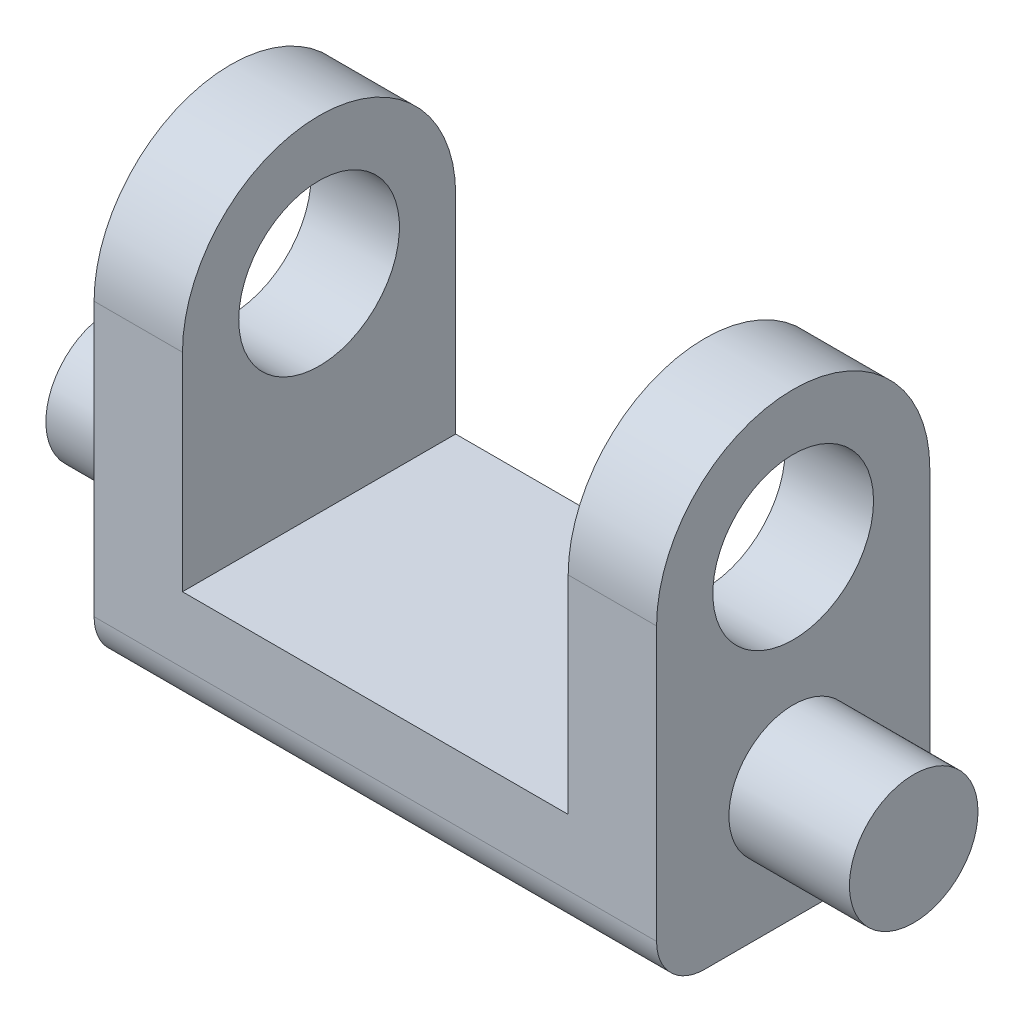
SolidWorks part; units mm, degrees
ref_plane "Front Plane" through (0, 0, 0) normal (0, 0, 1) x (1, 0, 0)
ref_plane "Top Plane" through (0, 0, 0) normal (0, 1, 0) x (1, 0, 0)
ref_plane "Right Plane" through (0, 0, 0) normal (1, 0, 0) x (0, 0, -1)
sketch "Sketch1" plane through (0, 0, 0) normal (1, 0, 0) x (0, 0, -1)
  circle A0 centre (0, 0) radius 8
  dimension "D1" = 16
extrude "Boss-Extrude1" add sketch "Sketch1" along normal mid plane 100
sketch "Sketch2" plane through (0, 0, 0) normal (1, 0, 0) x (0, 0, -1)
  line L0 (-11, -15) -> (11, -15)
  line L1 (17, -9) -> (17, 25)
  line L2 (-17, 25) -> (-17, -9)
  arc A0 (17, 25) -> (-17, 25) centre (0, 25) ccw
  arc A1 (11, -15) -> (17, -9) centre (11, -9) ccw
  arc A2 (-17, -9) -> (-11, -15) centre (-11, -9) ccw
  circle A3 centre (0, 25) radius 10
  point P6 (0, -15)
  dimension "D1" = 6
  dimension "D4" = 20
  dimension "D5" = 17
  dimension "D2" = 40
  dimension "D3" = 15
extrude "Boss-Extrude2" add sketch "Sketch2" along normal mid plane 70
ref_axis "Axis1" through (52.25, 0, 0) along (-1, 0, 0)
sketch "Sketch5" plane through (0, 0, 17) normal (0, 0, 1) x (1, 0, 0)
  line L1 (-24, -0.8133) -> (24, -0.8133)
  line L2 (-24, -0.8133) -> (-24, 42)
  line L3 (-24, 42) -> (24, 42)
  line L4 (24, -0.8133) -> (24, 42)
  point P4 (0, -0.8133)
  dimension "D1" = 48
extrude "Cut-Extrude1" cut sketch "Sketch5" against normal through all
